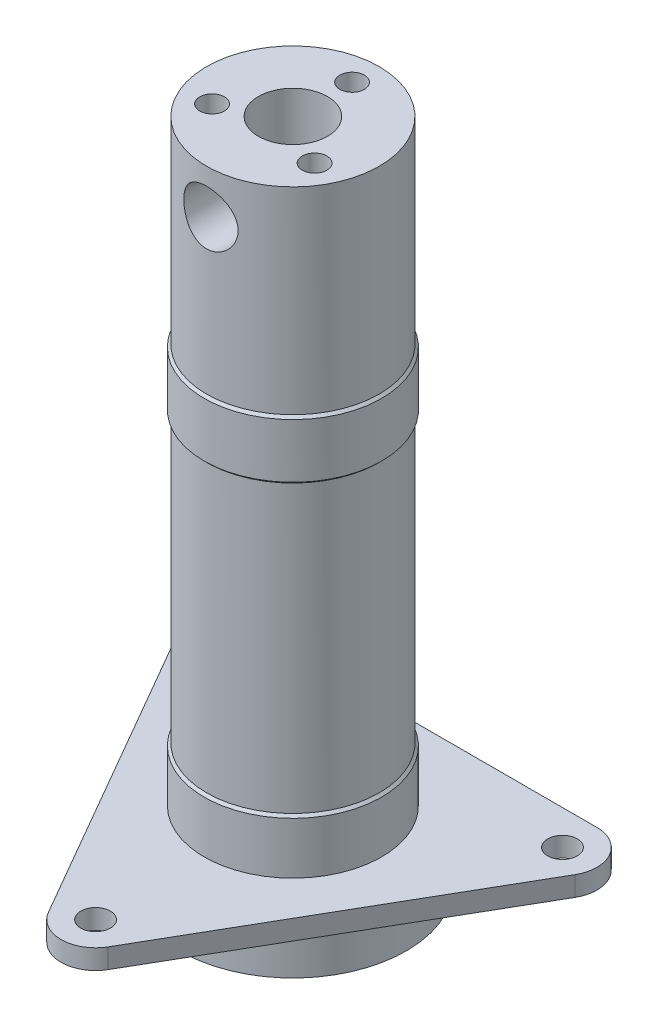
SolidWorks part; units mm, degrees
material "1060 合金"
ref_plane "前视基准面" through (0, 0, 0) normal (0, 0, 1) x (1, 0, 0)
ref_plane "上视基准面" through (0, 0, 0) normal (0, 1, 0) x (1, 0, 0)
ref_plane "右视基准面" through (0, 0, 0) normal (1, 0, 0) x (0, 0, -1)
sketch "草图2" plane through (0, 0, 0) normal (0, 0, 1) x (1, 0, 0)
  line L0 (0, 0) -> (0, 53) construction
  line L4 (9, 2) -> (9, 7)
  line L5 (8.75, 62.5) -> (3.5, 62.5)
  line L6 (3.5, 62.5) -> (3.5, 54)
  line L8 (23.5, 2) -> (23.5, 0)
  line L12 (23.5, 2) -> (9, 2)
  line L13 (6.5, 51) -> (6.5, -5)
  line L14 (11.5, 0) -> (11.5, -5)
  line L15 (11.5, -5) -> (6.5, -5)
  line L17 (11.5, 0) -> (23.5, 0)
  line L18 (8.75, 62.5) -> (8.75, 42)
  line L19 (8.75, 42) -> (9, 42)
  line L21 (6.5, 51) -> (3.5, 54)
  line L22 (9, 37) -> (9, 42)
  line L23 (9, 37) -> (8.75, 37)
  line L25 (9, 7) -> (8.75, 7)
  line L26 (8.75, 37) -> (8.75, 7)
  dimension "D1" = 13
  dimension "D2" = 2
  dimension "D3" = 23
  dimension "D4" = 18
  dimension "D5" = 23.5
  dimension "D6" = 7
  dimension "D7" = 20.5
  dimension "D8" = 5
  dimension "D9" = 5
  dimension "D10" = 17.5
  dimension "D11" = 40
  dimension "D12" = 5
  dimension "D13" = 135
  dimension "D14" = 8.5
revolve "旋转1" add sketch "草图2" angle 360 about L0
chamfer "倒角1" distance 0.5 angle 45 3 edges at (0, 42, -8.75) (0, 37, -8.75) (0, 7, -8.75)
chamfer "倒角2" distance 1 angle 45 1 edges at (0, 0, -11.5)
sketch "草图9" plane through (0, 0, 0) normal (0, -1, 0) x (1, 0, 0)
  line L0 (0, 0) -> (0, 20) construction
  line L1 (-3.0311, 21.75) -> (-20.3516, -8.25)
  line L2 (20.3516, -8.25) -> (3.0311, 21.75)
  line L3 (-17.3205, -13.5) -> (17.3205, -13.5)
  circle A0 centre (0, 20) radius 1.5
  circle A1 centre (17.3205, -10) radius 1.5
  circle A2 centre (-17.3205, -10) radius 1.5
  circle A3 centre (0, 0) radius 20 construction
  circle A4 centre (0, 0) radius 23.5 construction
  arc A5 (3.0311, 21.75) -> (-3.0311, 21.75) centre (0, 20) ccw
  arc A6 (17.3205, -13.5) -> (20.3516, -8.25) centre (17.3205, -10) ccw
  arc A7 (-20.3516, -8.25) -> (-17.3205, -13.5) centre (-17.3205, -10) ccw
  circle A8 centre (0, 0) radius 9 construction
  dimension "D2" = 3
  dimension "D4" = 18
  dimension "D1" = 40
  dimension "D3" = 3
extrude "切除-拉伸2" cut sketch "草图9" against normal through all flip side to cut
hole_wizard "M3 螺纹孔1" positions "草图13" profile "草图14" tap size "M3" standard "GB"
sketch "草图13" plane through (0, -5, 0) normal (0, 1, 0) x (1, 0, 0)
  circle A0 centre (0, 0) radius 9 construction
  point P0 (0, 9)
  point P10 (7.7942, -4.5)
  point P11 (-7.7942, -4.5)
  dimension "D1" = 18
  dimension "D2" = 3
cosmetic thread "孔螺蚊线1" parameters "D1"=4.5, "D2"=3
cosmetic thread "孔螺蚊线2" parameters "D1"=4.5, "D2"=3
cosmetic thread "孔螺蚊线3" parameters "D1"=4.5, "D2"=3
sketch "草图14" plane through (0, -5, -9) normal (1, 0, 0) x (0, 0, -1)
  line L0 (0, 0) -> (0, 5.7511)
  line L1 (0, 5.7511) -> (1.25, 5)
  line L2 (1.25, 5) -> (1.25, 0)
  line L5 (1.25, 0) -> (0, 0)
  line L10 (0, 5.7511) -> (-1.25, 5) construction
  line L11 (0, -6.35) -> (0, 107.95) construction
  dimension "螺纹孔钻头直径" = 2.5
  dimension "螺纹孔钻头深度" = 5
  dimension "导头角度" = 118
hole_wizard "M3 螺纹孔2" positions "草图15" profile "草图16" tap size "M3" standard "GB"
sketch "草图15" plane through (0, 62.5, 0) normal (0, 1, 0) x (1, 0, 0)
  circle A0 centre (0, 0) radius 6 construction
  circle A1 centre (0, 0) radius 9 construction
  point P0 (0, 6)
  point P14 (5.1962, -3)
  point P15 (-5.1962, -3)
  dimension "D1" = 3
  dimension "D2" = 3
cosmetic thread "孔螺蚊线4" parameters "D1"=6, "D2"=3
cosmetic thread "孔螺蚊线5" parameters "D1"=6, "D2"=3
cosmetic thread "孔螺蚊线6" parameters "D1"=6, "D2"=3
sketch "草图16" plane through (0, 62.5, -6) normal (1, 0, 0) x (0, 0, 1)
  line L0 (0, 0) -> (0, 7.2511)
  line L1 (0, 7.2511) -> (1.25, 6.5)
  line L2 (1.25, 6.5) -> (1.25, 0)
  line L5 (1.25, 0) -> (0, 0)
  line L10 (0, 7.2511) -> (-1.25, 6.5) construction
  line L11 (0, -6.35) -> (0, 107.95) construction
  dimension "螺纹孔钻头直径" = 2.5
  dimension "螺纹孔钻头深度" = 6.5
  dimension "导头角度" = 118
sketch "草图11" plane through (0, 0, 0) normal (0, 0, 1) x (1, 0, 0)
  line L0 (0, 0) -> (0, 62.5) construction
  line L5 (3.5, 62.5) -> (-3.5, 62.5) construction
  line L6 (8.75, 62.5) -> (-8.75, 62.5) construction
  circle A2 centre (0, 58) radius 2.75
  dimension "D1" = 5.5
  dimension "D2" = 4.5
extrude "切除-拉伸4" cut sketch "草图11" along normal through all
